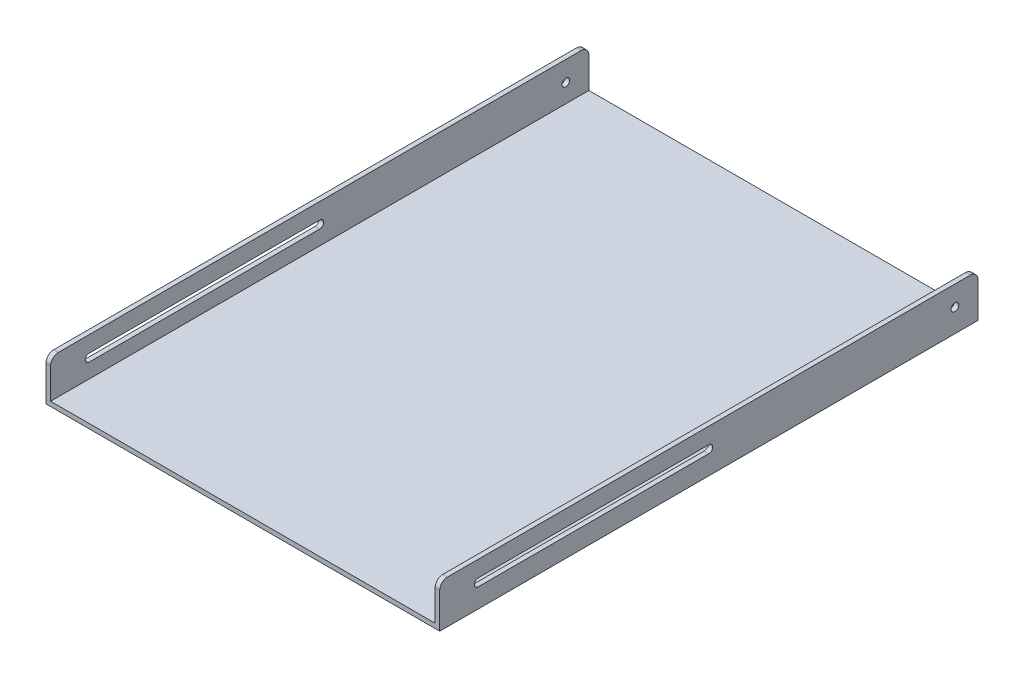
SolidWorks part; units mm, degrees
ref_plane "Front Plane" through (0, 0, 0) normal (0, 0, 1) x (1, 0, 0)
ref_plane "Top Plane" through (0, 0, 0) normal (0, 1, 0) x (1, 0, 0)
ref_plane "Right Plane" through (0, 0, 0) normal (1, 0, 0) x (0, 0, -1)
sketch "Sketch1" plane through (0, 0, 0) normal (0, 0, 1) x (1, 0, 0)
  line L0 (-250, 50) -> (-250, 0)
  line L1 (-250, 0) -> (250, 0)
  line L2 (250, 0) -> (250, 50)
  dimension "D1" = 500
  dimension "D2" = 50
  dimension "D3" = 50
  dimension "D4" = 250
extrude "Extrude-Thin1" add sketch "Sketch1" along normal mid plane 700 thin thin type one direction wall 6
sketch "Sketch2" plane through (256, 0, 0) normal (1, 0, 0) x (0, 0, -1)
  line L0 (350, -6) -> (350, 50) construction
  line L1 (-350, -6) -> (350, -6) construction
  line L2 (-300, 24) -> (0, 24) construction
  line L3 (-300, 29) -> (0, 29)
  line L4 (-300, 19) -> (0, 19)
  circle A0 centre (320, 24) radius 5
  arc A1 (-300, 29) -> (-300, 19) centre (-300, 24) ccw
  arc A2 (0, 19) -> (0, 29) centre (0, 24) ccw
  point P4 (350, 22)
  point P9 (-150, 24)
  dimension "D1" = 10
  dimension "D2" = 30
  dimension "D3" = 30
  dimension "D4" = 150
  dimension "D5" = 300
  dimension "D6" = 10
extrude "Cut-Extrude1" cut sketch "Sketch2" against normal through all
fillet "Fillet1" radius 10 4 edges at (253, 50, 350) (-253, 50, 350) (-253, 50, -350) (253, 50, -350)
ref_plane "Plane1" through (-256, 0, 0) normal (-1, 0, 0) x (0, 0, 1)
sketch "Sketch3" plane through (-256, 0, 0) normal (-1, 0, 0) x (0, 0, 1)
  arc A0 (0, 29) -> (0, 19) centre (0, 24) ccw construction
  arc A1 (0, 29) -> (0, 19) centre (0, 24) ccw
ref_axis "base_prismatic" through (-256, 24, 0) along (0, 0, 1)
sketch "Sketch5" plane through (-256, 0, 0) normal (-1, 0, 0) x (0, 0, 1)
  line L0 (350, 40) -> (350, -6) construction
  line L1 (350, -6) -> (-350, -6) construction
  line L2 (-350, 40) -> (-350, -6) construction
  line L3 (340, 50) -> (-340, 50) construction
  line L4 (350, 40) -> (350, -6)
  line L5 (350, -6) -> (-350, -6)
  line L6 (-350, 40) -> (-350, -6)
  line L7 (340, 50) -> (-340, 50)
  arc A0 (350, 40) -> (340, 50) centre (340, 40) ccw construction
  arc A1 (-340, 50) -> (-350, 40) centre (-340, 40) ccw construction
  arc A2 (350, 40) -> (340, 50) centre (340, 40) ccw
  arc A3 (-340, 50) -> (-350, 40) centre (-340, 40) ccw
  point P0 (300, 24)
  point P2 (0, 24)
  point P4 (-320, 24)
